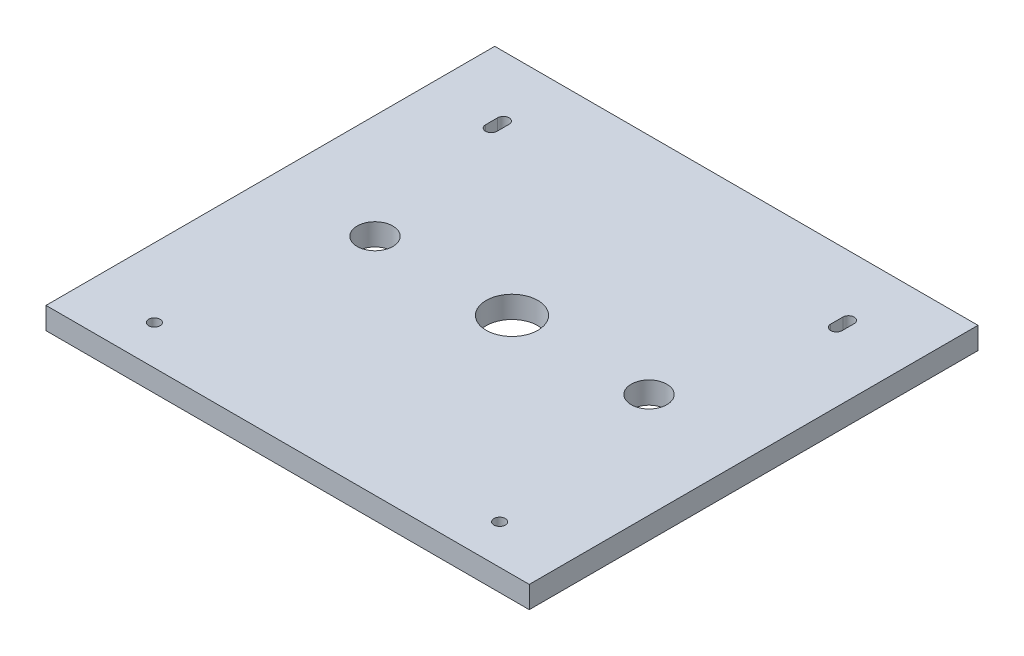
SolidWorks part; units mm, degrees
ref_plane "Front Plane" through (0, 0, 0) normal (0, 0, 1) x (1, 0, 0)
ref_plane "Top Plane" through (0, 0, 0) normal (0, 1, 0) x (1, 0, 0)
ref_plane "Right Plane" through (0, 0, 0) normal (1, 0, 0) x (0, 0, -1)
sketch "Sketch1" plane through (0, 0, 0) normal (0, 1, 0) x (1, 0, 0)
  line L1 (0, 0) -> (140, 0)
  line L2 (0, 0) -> (0, 130)
  line L3 (0, 130) -> (140, 130)
  line L4 (140, 0) -> (140, 130)
  dimension "D1" = 130
  dimension "D2" = 140
extrude "Boss-Extrude1" add sketch "Sketch1" along normal blind 6.35
sketch "Sketch2" plane through (0, 6.35, 0) normal (0, 1, 0) x (1, 0, 0)
  line L0 (0, 65) -> (140, 65) construction
  line L1 (0, 130) -> (0, 0) construction
  line L2 (140, 0) -> (140, 130) construction
  line L3 (70, 130) -> (70, 0) construction
  line L4 (140, 130) -> (0, 130) construction
  line L5 (0, 0) -> (140, 0) construction
  line L6 (0, 11.41) -> (140, 11.41) construction
  line L7 (0, 110.74) -> (140, 110.74) construction
  line L8 (120, 108.99) -> (120, 112.49) construction
  line L11 (20, 108.99) -> (20, 112.49) construction
  line L12 (18.35, 108.99) -> (18.35, 112.49)
  line L13 (21.65, 108.99) -> (21.65, 112.49)
  line L14 (121.65, 108.99) -> (121.65, 112.49)
  line L17 (118.35, 108.99) -> (118.35, 112.49)
  circle A0 centre (20, 11.41) radius 1.65
  arc A6 (18.35, 108.99) -> (21.65, 108.99) centre (20, 108.99) ccw
  arc A7 (21.65, 112.49) -> (18.35, 112.49) centre (20, 112.49) ccw
  circle A12 centre (70, 65) radius 7.5
  circle A15 centre (30.31, 65) radius 5.16
  circle A16 centre (120, 11.41) radius 1.65
  circle A17 centre (109.69, 65) radius 5.16
  arc A18 (121.65, 108.99) -> (118.35, 108.99) centre (120, 108.99) cw
  arc A19 (118.35, 112.49) -> (121.65, 112.49) centre (120, 112.49) cw
  point P26 (120, 110.74)
  point P33 (20, 110.74)
  dimension "D5" = 3.3
  dimension "D10" = 15
  dimension "D8" = 10.32
  dimension "D1" = 53.59
  dimension "D2" = 45.74
  dimension "D3" = 50
  dimension "D4" = 50
  dimension "D6" = 3.3
  dimension "D7" = 3.5
  dimension "D9" = 39.69
extrude "Cut-Extrude1" cut sketch "Sketch2" against normal through all
